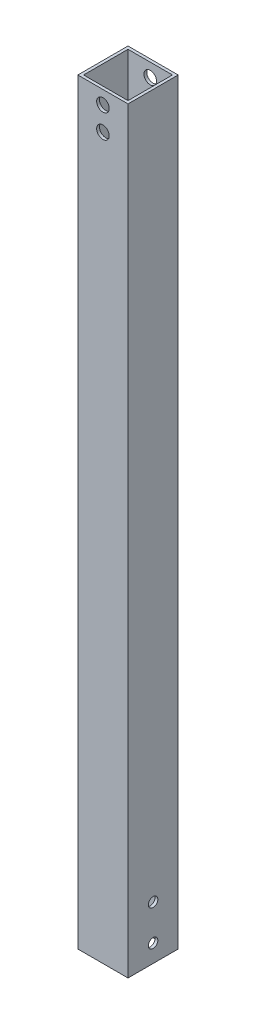
SolidWorks part; units mm, degrees
material "6061 Alloy"
ref_plane "Front Plane" through (0, 0, 0) normal (0, 0, 1) x (1, 0, 0)
ref_plane "Top Plane" through (0, 0, 0) normal (0, 1, 0) x (1, 0, 0)
ref_plane "Right Plane" through (0, 0, 0) normal (1, 0, 0) x (0, 0, -1)
sketch "Sketch1" plane through (0, 0, 0) normal (0, 1, 0) x (1, 0, 0)
  line L9 (12.7, -12.7) -> (-12.7, -12.7)
  line L10 (12.7, -12.7) -> (12.7, 12.7)
  line L11 (12.7, 12.7) -> (-12.7, 12.7)
  line L12 (-12.7, -12.7) -> (-12.7, 12.7)
  line L13 (12.7, -12.7) -> (-12.7, 12.7) construction
  line L14 (12.7, 12.7) -> (-12.7, -12.7) construction
  point P0 (0, 0)
  dimension "D1" = 25.4
extrude "Extrude-Thin1" add sketch "Sketch1" along normal blind 406.4 thin thin type mid plane wall 1.524
hole_wizard "1/4 Clearance Hole1" positions "Sketch2" profile "Sketch3" hole size "1/4" standard "ANSI Inch" end condition through all
sketch "Sketch2" plane through (0, 0, -13.462) normal (0, 0, -1) x (-1, 0, 0)
  point P0 (0, 399.2245)
  point P3 (0, 386.5245)
sketch "Sketch3" plane through (0, 399.2245, -13.462) normal (1, 0, 0) x (0, 1, 0)
  line L0 (0, 0) -> (0, 26.924)
  line L1 (0, 26.924) -> (3.3782, 26.924)
  line L2 (3.3782, 26.924) -> (3.3782, 0)
  line L5 (3.3782, 0) -> (0, 0)
  line L11 (0, -6.35) -> (0, 107.95) construction
  dimension "Thru Hole Dia." = 6.7564
  dimension "Thru Hole Depth" = 26.924
sketch "Sketch4" plane through (13.462, 0, 0) normal (1, 0, 0) x (0, 0, -1)
  line L0 (-13.462, 0) -> (13.462, 0) construction
  circle A0 centre (0, 9.525) radius 2.54
  circle A1 centre (0, 28.575) radius 2.54
  dimension "D1" = 5.08
  dimension "D2" = 9.525
  dimension "D3" = 28.575
hole_wizard "#10 Clearance Hole1" positions "Sketch5" profile "Sketch6" hole size "#10" standard "ANSI Inch" end condition through all
sketch "Sketch5" plane through (13.462, 0, 0) normal (1, 0, 0) x (0, 0, -1)
  point P0 (0, 9.525)
  point P3 (0, 28.575)
sketch "Sketch6" plane through (13.462, 9.525, 0) normal (0, 1, 0) x (0, 0, -1)
  line L0 (0, 0) -> (0, 26.924)
  line L1 (0, 26.924) -> (2.5527, 26.924)
  line L2 (2.5527, 26.924) -> (2.5527, 0)
  line L5 (2.5527, 0) -> (0, 0)
  line L11 (0, -6.35) -> (0, 107.95) construction
  dimension "Thru Hole Dia." = 5.1054
  dimension "Thru Hole Depth" = 26.924
